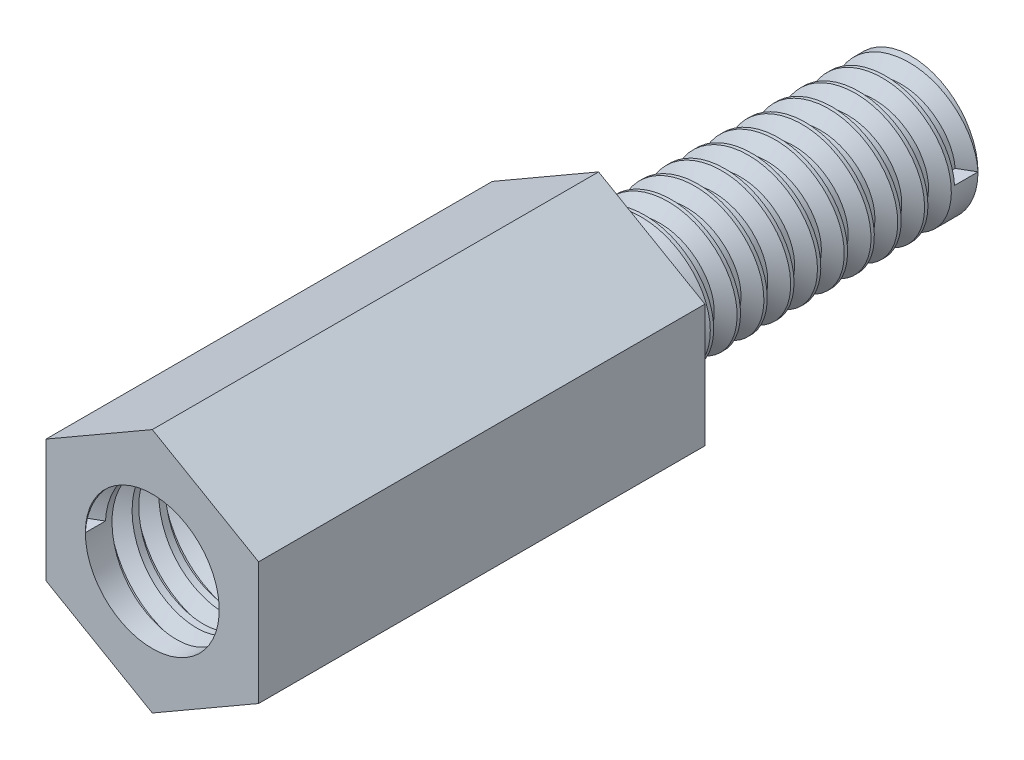
SolidWorks part; units mm, degrees
ref_plane "Front Plane" through (0, 0, 0) normal (0, 0, 1) x (1, 0, 0)
ref_plane "Top Plane" through (0, 0, 0) normal (0, 1, 0) x (1, 0, 0)
ref_plane "Right Plane" through (0, 0, 0) normal (1, 0, 0) x (0, 0, -1)
sketch "Sketch1" plane through (0, 0, 0) normal (0, 0, 1) x (1, 0, 0)
  line L1 (-2.3816, -1.375) -> (0, -2.75)
  line L2 (0, -2.75) -> (2.3816, -1.375)
  line L3 (2.3816, -1.375) -> (2.3816, 1.375)
  line L4 (2.3816, 1.375) -> (0, 2.75)
  line L5 (0, 2.75) -> (-2.3816, 1.375)
  line L6 (-2.3816, 1.375) -> (-2.3816, -1.375)
  circle A0 centre (0, 0) radius 2.3816 construction
  dimension "D1" = 5.5
extrude "Boss-Extrude1" add sketch "Sketch1" along normal blind 10
sketch "Sketch2" plane through (0, 0, 10) normal (0, 0, 1) x (1, 0, 0)
  circle A0 centre (0, 0) radius 1.5
  dimension "D1" = 3
extrude "Cut-Extrude1" cut sketch "Sketch2" against normal blind 7
sketch "Sketch3" plane through (0, 0, 0) normal (0, 0, -1) x (-1, 0, 0)
  circle A0 centre (0, 0) radius 1.5
  dimension "D1" = 3
extrude "Boss-Extrude2" add sketch "Sketch3" along normal blind 7
thread "Thread1" pitch 0.6 method cut profile "Thread Profile1" start angle 0, offset 0, length 0, pitch 0.6, diameter 3
ref_plane "Plane1" through (1.5, 0, -7) normal (0, -1, 0) x (1, 0, 0)
sketch "Thread Profile1" plane through (1.5, 0, -7) normal (0, -1, 0) x (1, 0, 0)
  line L0 (0, 0) -> (0, 0.6) construction
  line L11 (0, 0) -> (0, 0.525)
  line L12 (0, 0.525) -> (-0.3248, 0.3375)
  line L13 (-0.3248, 0.3375) -> (-0.3248, 0.1875)
  line L15 (-0.3248, 0.1875) -> (0, 0)
  line L17 (-0.3248, 0.2625) -> (0, 0.2625) construction
  point P2 (0, 0)
  dimension "Pitch" = 0.6
  dimension "Profile_Angle" = 60
  dimension "Profile_Land" = 0.15
  dimension "Profile_Height" = 0.3248
thread "Thread2" pitch 0.6 method cut profile "Thread Profile2" start angle 0, offset 0, length 0, pitch 0.6, diameter 3
ref_plane "Plane2" through (-1.5, 0, 10) normal (0, -1, 0) x (-1, 0, 0)
sketch "Thread Profile2" plane through (-1.5, 0, 10) normal (0, -1, 0) x (-1, 0, 0)
  line L0 (0, 0) -> (0, 0.6) construction
  line L1 (0, 0) -> (0.3248, 0.1875)
  line L2 (0.3248, 0.1875) -> (0.3248, 0.2625)
  line L3 (0.3248, 0.2625) -> (0, 0.45)
  line L4 (0.3248, 0.225) -> (0, 0.225) construction
  line L11 (0, 0) -> (0, 0.45)
  point P2 (0, 0)
  dimension "Pitch" = 0.6
  dimension "Profile_Angle" = 60
  dimension "Profile_Land" = 0.075
  dimension "Profile_Height" = 0.3248
